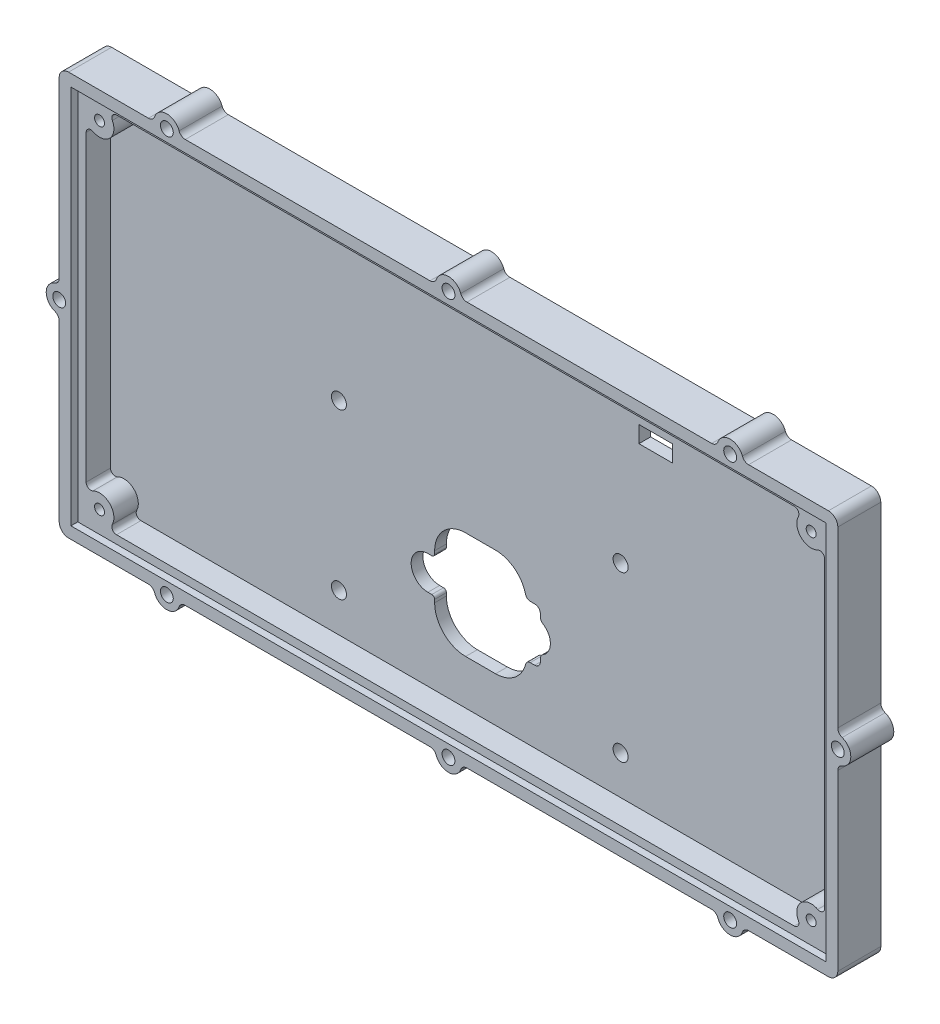
SolidWorks part; units mm, degrees
ref_plane "Front Plane" through (0, 0, 0) normal (0, 0, 1) x (1, 0, 0)
ref_plane "Top Plane" through (0, 0, 0) normal (0, 1, 0) x (1, 0, 0)
ref_plane "Right Plane" through (0, 0, 0) normal (1, 0, 0) x (0, 0, -1)
sketch "PCB" plane through (0, 0, 0) normal (0, 0, 1) x (1, 0, 0)
  line L0 (96.2635, 45.5524) -> (101.8921, 45.5524) construction
  line L1 (-101.8921, 51.181) -> (101.8921, 51.181) construction
  line L2 (-101.8921, 51.181) -> (-101.8921, -51.181) construction
  line L3 (-101.8921, -51.181) -> (101.8921, -51.181) construction
  line L4 (101.8921, 51.181) -> (101.8921, -51.181) construction
  line L5 (-101.8921, 51.181) -> (101.8921, -51.181) construction
  line L6 (-101.8921, -51.181) -> (101.8921, 51.181) construction
  line L7 (96.2635, 45.5524) -> (96.2635, 51.181) construction
  line L8 (-96.2635, 45.5524) -> (-101.8921, 45.5524) construction
  line L9 (-96.2635, -45.5524) -> (-96.2635, -51.181) construction
  line L10 (-92.8243, 0) -> (-92.8243, 25.6794) construction
  line L11 (-98.8568, 31.7119) -> (-86.7918, 31.7119)
  line L12 (-98.8568, 31.7119) -> (-98.8568, 19.6469)
  line L13 (-98.8568, 19.6469) -> (-86.7918, 19.6469)
  line L14 (-86.7918, 31.7119) -> (-86.7918, 19.6469)
  line L15 (-98.8568, 31.7119) -> (-86.7918, 19.6469) construction
  line L16 (-98.8568, 19.6469) -> (-86.7918, 31.7119) construction
  line L17 (-98.8568, 6.0325) -> (-86.7918, 6.0325)
  line L18 (-98.8568, 6.0325) -> (-98.8568, -6.0325)
  line L19 (-98.8568, -6.0325) -> (-86.7918, -6.0325)
  line L20 (-86.7918, 6.0325) -> (-86.7918, -6.0325)
  line L21 (-98.8568, 6.0325) -> (-86.7918, -6.0325) construction
  line L22 (-98.8568, -6.0325) -> (-86.7918, 6.0325) construction
  line L23 (-98.8568, -19.6469) -> (-86.7918, -19.6469)
  line L24 (-98.8568, -19.6469) -> (-98.8568, -31.7119)
  line L25 (-98.8568, -31.7119) -> (-86.7918, -31.7119)
  line L26 (-86.7918, -19.6469) -> (-86.7918, -31.7119)
  line L27 (-98.8568, -19.6469) -> (-86.7918, -31.7119) construction
  line L28 (-98.8568, -31.7119) -> (-86.7918, -19.6469) construction
  line L29 (86.7918, 31.7119) -> (98.8568, 31.7119)
  line L30 (86.7918, 31.7119) -> (86.7918, 19.6469)
  line L31 (86.7918, 19.6469) -> (98.8568, 19.6469)
  line L32 (98.8568, 31.7119) -> (98.8568, 19.6469)
  line L33 (86.7918, 31.7119) -> (98.8568, 19.6469) construction
  line L34 (86.7918, 19.6469) -> (98.8568, 31.7119) construction
  line L35 (86.7918, 6.0325) -> (98.8568, 6.0325)
  line L36 (86.7918, 6.0325) -> (86.7918, -6.0325)
  line L37 (86.7918, -6.0325) -> (98.8568, -6.0325)
  line L38 (98.8568, 6.0325) -> (98.8568, -6.0325)
  line L39 (86.7918, 6.0325) -> (98.8568, -6.0325) construction
  line L40 (86.7918, -6.0325) -> (98.8568, 6.0325) construction
  line L41 (86.7918, -19.6469) -> (98.8568, -19.6469)
  line L42 (86.7918, -19.6469) -> (86.7918, -31.7119)
  line L43 (86.7918, -31.7119) -> (98.8568, -31.7119)
  line L44 (98.8568, -19.6469) -> (98.8568, -31.7119)
  line L45 (86.7918, -19.6469) -> (98.8568, -31.7119) construction
  line L46 (86.7918, -31.7119) -> (98.8568, -19.6469) construction
  line L47 (-92.8243, 0) -> (-92.8243, -25.6794) construction
  line L48 (-92.8243, 25.6794) -> (-101.8921, 25.6794) construction
  line L49 (92.8243, 25.6794) -> (101.8921, 25.6794) construction
  line L50 (-3.114, -17.4711) -> (-3.114, -27.7327) construction
  circle A0 centre (-96.2635, 45.5524) radius 0.9995
  circle A1 centre (-96.2635, -45.5524) radius 0.9995
  circle A2 centre (96.2635, -45.5524) radius 0.9995
  circle A3 centre (96.2635, 45.5524) radius 0.9995
  circle A4 centre (-3.114, -17.4711) radius 1.9939
  circle A5 centre (-3.114, -27.7327) radius 1.9939
  point P0 (0, 0)
  point P14 (-92.8243, 25.6794)
  point P23 (-92.8243, 0)
  point P28 (-92.8243, -25.6794)
  point P33 (92.8243, 25.6794)
  point P38 (92.8243, 0)
  point P43 (92.8243, -25.6794)
  point P54 (0.1092, -22.6019)
  point P55 (-7.5006, -22.6019)
  point P60 (-3.114, -22.6019)
  dimension "D4" = 1.999
  dimension "D14" = 3.9878
  dimension "D1" = 203.7842
  dimension "D2" = 102.362
  dimension "D3" = 5.6286
  dimension "D5" = 25.5016
  dimension "D6" = 25.5016
  dimension "D7" = 9.0678
  dimension "D8" = 12.065
  dimension "D9" = 102.0013
  dimension "D10" = 28.5791
  dimension "D11" = 7.6098
  dimension "D12" = 5.1308
  dimension "D13" = 3.2233
sketch "DT_plug" plane through (0, 0, 0) normal (0, 0, 1) x (1, 0, 0)
  line L0 (29.2774, -40.0231) -> (29.2774, -5.0981) construction
  dimension "D1" = 34.925
sketch "display_screen" plane through (0, 0, 0) normal (0, 0, 1) x (1, 0, 0)
  line L1 (-80.3275, 46.3296) -> (83.7565, 46.3296) construction
  line L2 (-80.3275, 46.3296) -> (-80.3275, -50.9016) construction
  line L3 (-80.3275, -50.9016) -> (83.7565, -50.9016) construction
  line L4 (83.7565, 46.3296) -> (83.7565, -50.9016) construction
  line L5 (-78.2955, 44.2976) -> (78.2955, 44.2976) construction
  line L6 (-78.2955, 44.2976) -> (-78.2955, -44.2976) construction
  line L7 (-78.2955, -44.2976) -> (78.2955, -44.2976) construction
  line L8 (78.2955, 44.2976) -> (78.2955, -44.2976) construction
  point P8 (0, 44.2976)
  point P10 (-78.2955, 0)
  dimension "D1" = 164.084
  dimension "D2" = 97.2312
  dimension "D3" = 6.604
  dimension "D4" = 2.032
  dimension "D5" = 2.032
  dimension "D6" = 5.461
ref_plane "back_of_PCB" through (0, 0, -1.8542) normal (0, 0, 1) x (1, 0, 0)
ref_plane "back_PCB_clearance" through (0, 0, -8.4582) normal (0, 0, 1) x (1, 0, 0)
sketch "Sketch4" plane through (0, 0, 0) normal (0, 0, 1) x (1, 0, 0)
  line L0 (-102.1461, 51.4096) -> (-102.1461, 54.5846) construction
  line L1 (-102.1461, 51.4096) -> (102.1461, 51.4096)
  line L2 (-102.1461, 51.4096) -> (-102.1461, -51.4096)
  line L3 (-102.1461, -51.4096) -> (102.1461, -51.4096)
  line L4 (102.1461, 51.4096) -> (102.1461, -51.4096)
  line L5 (-105.3211, 54.5846) -> (105.3211, 54.5846)
  line L6 (-105.3211, 54.5846) -> (-105.3211, -54.5846)
  line L7 (-105.3211, -54.5846) -> (105.3211, -54.5846)
  line L8 (105.3211, 54.5846) -> (105.3211, -54.5846)
  line L9 (-102.1461, 51.4096) -> (-105.3211, 51.4096) construction
  line L10 (102.1461, -51.4096) -> (102.1461, -54.5846) construction
  line L11 (102.1461, -51.4096) -> (105.3211, -51.4096) construction
  line L12 (-101.8921, 51.181) -> (101.8921, 51.181) construction
  line L13 (-101.8921, 51.181) -> (-101.8921, -51.181) construction
  line L14 (101.8921, 51.181) -> (101.8921, -51.181) construction
  line L15 (-101.8921, -51.181) -> (101.8921, -51.181) construction
  dimension "D1" = 3.175
  dimension "D2" = 0.2286
  dimension "D3" = 0.254
  dimension "D4" = 0.254
  dimension "D5" = 0.2286
extrude "Boss-Extrude1" add sketch "Sketch4" against normal up to surface (1.8542 mm away) up to plane "back_of_PCB"
sketch "Sketch5" plane through (0, 0, -1.8542) normal (0, 0, -1) x (-1, 0, 0)
  line L1 (-105.3211, 54.5846) -> (105.3211, 54.5846)
  line L2 (-105.3211, 54.5846) -> (-105.3211, -54.5846)
  line L3 (-105.3211, -54.5846) -> (105.3211, -54.5846)
  line L4 (105.3211, 54.5846) -> (105.3211, -54.5846)
  line L6 (101.8921, 51.181) -> (-101.8921, 51.181) construction
  line L7 (-99.8931, 49.182) -> (99.8931, 49.182)
  line L8 (-99.8931, 49.182) -> (-99.8931, -49.182)
  line L9 (-99.8931, -49.182) -> (99.8931, -49.182)
  line L10 (99.8931, 49.182) -> (99.8931, -49.182)
  line L11 (-99.8931, 49.182) -> (-99.8931, 51.181) construction
  line L12 (-99.8931, 49.182) -> (-101.8921, 49.182) construction
  line L13 (-101.8921, 51.181) -> (-101.8921, -51.181) construction
  line L14 (99.8931, -49.182) -> (101.8921, -49.182) construction
  line L15 (101.8921, 51.181) -> (101.8921, -51.181) construction
  line L16 (99.8931, -49.182) -> (99.8931, -51.181) construction
  line L17 (101.8921, -51.181) -> (-101.8921, -51.181) construction
  dimension "D1" = 1.999
extrude "Boss-Extrude2" add sketch "Sketch5" along normal up to surface (6.604 mm away) up to plane "back_PCB_clearance"
sketch "Sketch6" plane through (0, 0, -8.4582) normal (0, 0, -1) x (-1, 0, 0)
  line L0 (11.7018, -27.8978) -> (11.7018, -28.6979) construction
  line L1 (-105.3211, 54.5846) -> (105.3211, 54.5846)
  line L2 (-105.3211, 54.5846) -> (-105.3211, -54.5846)
  line L3 (-105.3211, -54.5846) -> (105.3211, -54.5846)
  line L4 (105.3211, 54.5846) -> (105.3211, -54.5846)
  line L5 (3.8278, -8.6319) -> (-4.2865, -8.6319) construction
  line L6 (11.7018, -16.5059) -> (11.7018, -17.306) construction
  line L7 (3.8278, -36.5719) -> (-4.2865, -36.5719) construction
  line L9 (-43.0581, 40.7162) -> (-52.1081, 40.7162)
  line L10 (-43.0581, 40.7162) -> (-43.0581, 36.2153)
  line L11 (12.9718, -18.576) -> (14.0259, -18.576) construction
  line L12 (-43.0581, 36.2153) -> (-52.1081, 36.2153)
  line L13 (12.9718, -26.6278) -> (14.0259, -26.6278) construction
  line L14 (-52.1081, 40.7162) -> (-52.1081, 36.2153)
  line L15 (-13.6655, -15.9344) -> (-14.8666, -15.9344) construction
  line L16 (-15.8826, -27.4219) -> (-15.8826, -28.2534) construction
  line L17 (-13.6655, -29.2694) -> (-14.8666, -29.2694) construction
  line L18 (-15.8826, -16.9504) -> (-15.8826, -17.782) construction
  line L19 (-101.8921, 51.181) -> (-101.8921, -51.181) construction
  line L20 (12.2098, -27.8978) -> (12.2098, -28.6979)
  line L21 (3.8278, -37.0799) -> (-4.2865, -37.0799)
  line L22 (-13.6655, -29.7774) -> (-14.8666, -29.7774)
  line L23 (-16.3906, -27.4219) -> (-16.3906, -28.2534)
  line L24 (-16.3906, -16.9504) -> (-16.3906, -17.782)
  line L25 (-13.6655, -15.4264) -> (-14.8666, -15.4264)
  line L26 (3.8278, -8.1239) -> (-4.2865, -8.1239)
  line L27 (12.2098, -16.5059) -> (12.2098, -17.306)
  line L28 (12.9718, -18.068) -> (14.0259, -18.068)
  line L29 (12.9718, -27.1358) -> (14.0259, -27.1358)
  line L30 (-102.1461, 51.4096) -> (102.1461, 51.4096) construction
  arc A0 (-16.7989, -19.407) -> (-16.7989, -25.7969) centre (-14.8666, -22.6019) ccw construction
  arc A1 (12.9718, -18.576) -> (11.7018, -17.306) centre (12.9718, -17.306) cw construction
  arc A2 (12.9718, -26.6278) -> (11.7018, -27.8978) centre (12.9718, -27.8978) ccw construction
  arc A3 (14.0259, -26.6278) -> (14.0259, -18.576) centre (14.0259, -22.6019) ccw construction
  arc A4 (11.7018, -28.6979) -> (3.8278, -36.5719) centre (3.8278, -28.6979) cw construction
  arc A5 (11.7018, -16.5059) -> (3.8278, -8.6319) centre (3.8278, -16.5059) ccw construction
  arc A6 (-4.2865, -8.6319) -> (-11.9202, -14.5755) centre (-4.2865, -16.5059) ccw construction
  arc A7 (-11.9202, -14.5755) -> (-13.6655, -15.9344) centre (-13.6655, -14.1342) cw construction
  arc A8 (-4.2865, -36.5719) -> (-11.9202, -30.6283) centre (-4.2865, -28.6979) cw construction
  arc A9 (-11.9202, -30.6283) -> (-13.6655, -29.2694) centre (-13.6655, -31.0697) ccw construction
  arc A10 (-14.8666, -15.9344) -> (-15.8826, -16.9504) centre (-14.8666, -16.9504) ccw construction
  arc A11 (-15.8826, -17.782) -> (-16.7989, -19.407) centre (-17.7817, -17.782) cw construction
  arc A12 (-15.8826, -27.4219) -> (-16.7989, -25.7969) centre (-17.7817, -27.4219) ccw construction
  arc A13 (-15.8826, -28.2534) -> (-14.8666, -29.2694) centre (-14.8666, -28.2534) ccw construction
  arc A14 (12.2098, -28.6979) -> (3.8278, -37.0799) centre (3.8278, -28.6979) cw
  arc A15 (-4.2865, -37.0799) -> (-12.4127, -30.7529) centre (-4.2865, -28.6979) cw
  arc A16 (-12.4127, -30.7529) -> (-13.6655, -29.7774) centre (-13.6655, -31.0697) ccw
  arc A17 (-16.3906, -28.2534) -> (-14.8666, -29.7774) centre (-14.8666, -28.2534) ccw
  arc A18 (-16.3906, -27.4219) -> (-17.0618, -26.2315) centre (-17.7817, -27.4219) ccw
  arc A19 (-17.0618, -18.9723) -> (-17.0618, -26.2315) centre (-14.8666, -22.6019) ccw
  arc A20 (-16.3906, -17.782) -> (-17.0618, -18.9723) centre (-17.7817, -17.782) cw
  arc A21 (-14.8666, -15.4264) -> (-16.3906, -16.9504) centre (-14.8666, -16.9504) ccw
  arc A22 (-12.4127, -14.451) -> (-13.6655, -15.4264) centre (-13.6655, -14.1342) cw
  arc A23 (-4.2865, -8.1239) -> (-12.4127, -14.451) centre (-4.2865, -16.5059) ccw
  arc A24 (12.2098, -16.5059) -> (3.8278, -8.1239) centre (3.8278, -16.5059) ccw
  arc A25 (12.9718, -18.068) -> (12.2098, -17.306) centre (12.9718, -17.306) cw
  arc A26 (14.0259, -27.1358) -> (14.0259, -18.068) centre (14.0259, -22.6019) ccw
  arc A27 (12.9718, -27.1358) -> (12.2098, -27.8978) centre (12.9718, -27.8978) ccw
  point P6 (-0.1092, -22.6019)
  dimension "D7" = 3.7338
  dimension "D9" = 1.27
  dimension "D3" = 1.0541
  dimension "D10" = 7.874
  dimension "D13" = 1.8002
  dimension "D16" = 1.016
  dimension "D17" = 1.8991
  dimension "D2" = 11.811
  dimension "D4" = 13.97
  dimension "D5" = 15.7734
  dimension "D6" = 6.6675
  dimension "D8" = 1.016
  dimension "D11" = 0.8001
  dimension "D12" = 13.97
  dimension "D14" = 8.1143
  dimension "D15" = 6.6675
  dimension "D18" = 10.6934
  dimension "D19" = 49.784
  dimension "D20" = 9.05
  dimension "D21" = 4.5009
  dimension "D22" = 0.508
extrude "Boss-Extrude3" add sketch "Sketch6" along normal blind 3.175
sketch "Sketch9" plane through (0, 0, -1.8542) normal (0, 0, 1) x (1, 0, 0)
  line L2 (-99.8931, 49.182) -> (99.8931, 49.182) construction
  line L3 (99.8931, 49.182) -> (-99.8931, 49.182) construction
  line L4 (-99.8931, -49.182) -> (-99.8931, 49.182) construction
  line L6 (-99.8931, 40.9678) -> (-99.8931, 49.182)
  line L7 (-99.8931, 49.182) -> (-91.6789, 49.182)
  line L8 (-99.8931, -49.182) -> (99.8931, -49.182) construction
  line L9 (-99.8931, -40.9678) -> (-99.8931, -49.182)
  line L10 (-99.8931, -49.182) -> (-91.6789, -49.182)
  line L11 (99.8931, -49.182) -> (-99.8931, -49.182) construction
  line L12 (99.8931, -49.182) -> (99.8931, 49.182) construction
  line L13 (99.8931, -40.9678) -> (99.8931, -49.182)
  line L14 (99.8931, -49.182) -> (91.6789, -49.182)
  line L15 (91.6789, 49.182) -> (99.8931, 49.182)
  line L16 (99.8931, 49.182) -> (99.8931, 40.9678)
  circle A0 centre (-96.2635, 45.5524) radius 1.3462
  arc A1 (-98.0419, 42.097) -> (-92.8081, 47.3308) centre (-96.2635, 45.5524) ccw
  arc A3 (-92.8081, 47.3308) -> (-91.6789, 49.182) centre (-91.6789, 47.912) cw
  arc A4 (-98.0419, 42.097) -> (-99.8931, 40.9678) centre (-98.6231, 40.9678) ccw
  circle A5 centre (-96.2635, -45.5524) radius 1.3462
  arc A6 (-92.8081, -47.3308) -> (-98.0419, -42.097) centre (-96.2635, -45.5524) ccw
  arc A7 (-98.0419, -42.097) -> (-99.8931, -40.9678) centre (-98.6231, -40.9678) cw
  arc A8 (-92.8081, -47.3308) -> (-91.6789, -49.182) centre (-91.6789, -47.912) ccw
  circle A9 centre (96.2635, -45.5524) radius 1.3462
  arc A10 (98.0419, -42.097) -> (92.8081, -47.3308) centre (96.2635, -45.5524) ccw
  arc A11 (92.8081, -47.3308) -> (91.6789, -49.182) centre (91.6789, -47.912) cw
  arc A12 (98.0419, -42.097) -> (99.8931, -40.9678) centre (98.6231, -40.9678) ccw
  circle A13 centre (96.2635, 45.5524) radius 1.3462
  arc A14 (92.8081, 47.3308) -> (98.0419, 42.097) centre (96.2635, 45.5524) ccw
  arc A15 (91.6789, 49.182) -> (92.8081, 47.3308) centre (91.6789, 47.912) cw
  arc A16 (98.0419, 42.097) -> (99.8931, 40.9678) centre (98.6231, 40.9678) cw
  dimension "D1" = 2.54
  dimension "D2" = 1.27
  dimension "D3" = 2.6924
extrude "Boss-Extrude4" add sketch "Sketch9" against normal up to surface (6.604 mm away) up to face at (0, 0, -8.4582)
extrude "Cut-Extrude3" cut sketch "Sketch9<2>" against normal up to surface (9.779 mm away) contours A5 | A0 | A13 | A9 up to face at (0, 0, -11.6332)
sketch "Sketch9<2>" plane through (0, 0, -1.8542) normal (0, 0, 1) x (1, 0, 0) same geometry as "Sketch9"
sketch "Sketch10" plane through (0, 0, -11.6332) normal (0, 0, -1) x (-1, 0, 0)
  line L0 (-38.1, 5.7404) -> (38.1, 5.7404) construction
  line L1 (38.1, 5.7404) -> (38.1, -38.7096) construction
  line L2 (-105.3211, -54.5846) -> (105.3211, -54.5846) construction
  circle A0 centre (-38.1, 5.7404) radius 2.032
  circle A1 centre (-38.1, 5.7404) radius 5.207 construction
  circle A2 centre (-38.1, -38.7096) radius 5.207 construction
  circle A3 centre (-38.1, -38.7096) radius 2.032
  circle A4 centre (38.1, -38.7096) radius 2.032
  circle A5 centre (38.1, -38.7096) radius 5.207 construction
  circle A6 centre (38.1, 5.7404) radius 2.032
  circle A7 centre (38.1, 5.7404) radius 5.207 construction
  point P12 (0, 5.7404)
  dimension "D1" = 4.064
  dimension "D2" = 3.175
  dimension "D3" = 76.2
  dimension "D4" = 44.45
  dimension "D5" = 15.875
extrude "Cut-Extrude1" cut sketch "Sketch10" against normal up to next
sketch "Sketch11" plane through (0, 0, 0) normal (0, 0, 1) x (1, 0, 0)
  line L2 (105.3211, 54.5846) -> (-105.3211, 54.5846) construction
  line L3 (-4.9885, 54.5846) -> (-4.9885, 51.5366)
  line L4 (-4.9885, 51.5366) -> (4.9885, 51.5366)
  line L5 (4.9885, 51.5366) -> (4.9885, 54.5846)
  line L6 (71.2115, 54.5846) -> (71.2115, 51.5366)
  line L7 (71.2115, 51.5366) -> (81.1885, 51.5366)
  line L8 (81.1885, 51.5366) -> (81.1885, 54.5846)
  line L9 (-71.2115, 54.5846) -> (-71.2115, 51.5366)
  line L10 (-71.2115, 51.5366) -> (-81.1885, 51.5366)
  line L11 (-81.1885, 51.5366) -> (-81.1885, 54.5846)
  line L12 (-76.2, 54.5846) -> (0, 54.5846) construction
  line L13 (0, 54.5846) -> (76.2, 54.5846) construction
  circle A0 centre (-76.2, 54.5846) radius 1.7399
  circle A1 centre (0, 54.5846) radius 1.7399
  circle A2 centre (76.2, 54.5846) radius 1.7399
  arc A3 (-81.1885, 54.5846) -> (-79.5137, 55.7657) centre (-81.1885, 56.3626) ccw
  arc A4 (-79.5137, 55.7657) -> (-72.8863, 55.7657) centre (-76.2, 54.5846) cw
  arc A5 (-72.8863, 55.7657) -> (-71.2115, 54.5846) centre (-71.2115, 56.3626) ccw
  arc A6 (71.2115, 54.5846) -> (72.8863, 55.7657) centre (71.2115, 56.3626) ccw
  arc A7 (72.8863, 55.7657) -> (79.5137, 55.7657) centre (76.2, 54.5846) cw
  arc A8 (-3.3137, 55.7657) -> (3.3137, 55.7657) centre (0, 54.5846) cw
  arc A9 (-3.3137, 55.7657) -> (-4.9885, 54.5846) centre (-4.9885, 56.3626) cw
  arc A10 (3.3137, 55.7657) -> (4.9885, 54.5846) centre (4.9885, 56.3626) ccw
  arc A11 (79.5137, 55.7657) -> (81.1885, 54.5846) centre (81.1885, 56.3626) ccw
  dimension "D1" = 3.4798
  dimension "D3" = 1.778
  dimension "D4" = 1.778
  dimension "D5" = 3.048
  dimension "D6" = 76.2
extrude "Cut-Extrude2" cut sketch "Sketch11" against normal up to next contours A2 | A1 | A0
extrude "Boss-Extrude5" add sketch "Sketch11<3>" against normal up to surface (11.6332 mm away) up to face at (0, 32.2288, -11.6332)
sketch "Sketch11<3>" plane through (0, 0, 0) normal (0, 0, 1) x (1, 0, 0) same geometry as "Sketch11"
mirror "Mirror1" about plane through (0, 0, 0) normal (0, 1, 0) of "Boss-Extrude5", "Cut-Extrude2"
sketch "Sketch12" plane through (0, 0, 0) normal (0, 0, 1) x (1, 0, 0)
  line L0 (-105.3211, 54.5846) -> (-105.3211, -54.5846) construction
  line L2 (-105.3211, 4.9885) -> (-102.2731, 4.9885)
  line L3 (-102.2731, 4.9885) -> (-102.2731, -4.9885)
  line L4 (-102.2731, -4.9885) -> (-105.3211, -4.9885)
  line L5 (-4.9885, 54.5846) -> (-4.9885, 51.5366) construction
  circle A0 centre (-105.3211, 0) radius 1.7399
  arc A1 (-106.5022, 3.3137) -> (-106.5022, -3.3137) centre (-105.3211, 0) ccw
  arc A2 (-106.5022, -3.3137) -> (-105.3211, -4.9885) centre (-107.0991, -4.9885) cw
  arc A3 (-106.5022, 3.3137) -> (-105.3211, 4.9885) centre (-107.0991, 4.9885) ccw
  circle A4 centre (0, 54.5846) radius 1.7399 construction
  arc A5 (3.3137, 55.7657) -> (4.9885, 54.5846) centre (4.9885, 56.3626) ccw construction
  dimension "D2" = 1.778
extrude "Cut-Extrude4" cut sketch "Sketch12" against normal up to next contours A0
extrude "Boss-Extrude6" add sketch "Sketch12<3>" against normal up to surface (11.6332 mm away) up to face at (-6.9634, 0, -11.6332)
sketch "Sketch12<3>" plane through (0, 0, 0) normal (0, 0, 1) x (1, 0, 0) same geometry as "Sketch12"
mirror "Mirror2" about plane through (0, 0, 0) normal (1, 0, 0) of "Boss-Extrude6", "Cut-Extrude4"
fillet "Fillet1" radius 2.54 4 edges at (105.3211, 54.5846, -5.8166) (105.3211, -54.5846, -5.8166) (-105.3211, -54.5846, -5.8166) (-105.3211, 54.5846, -5.8166)
